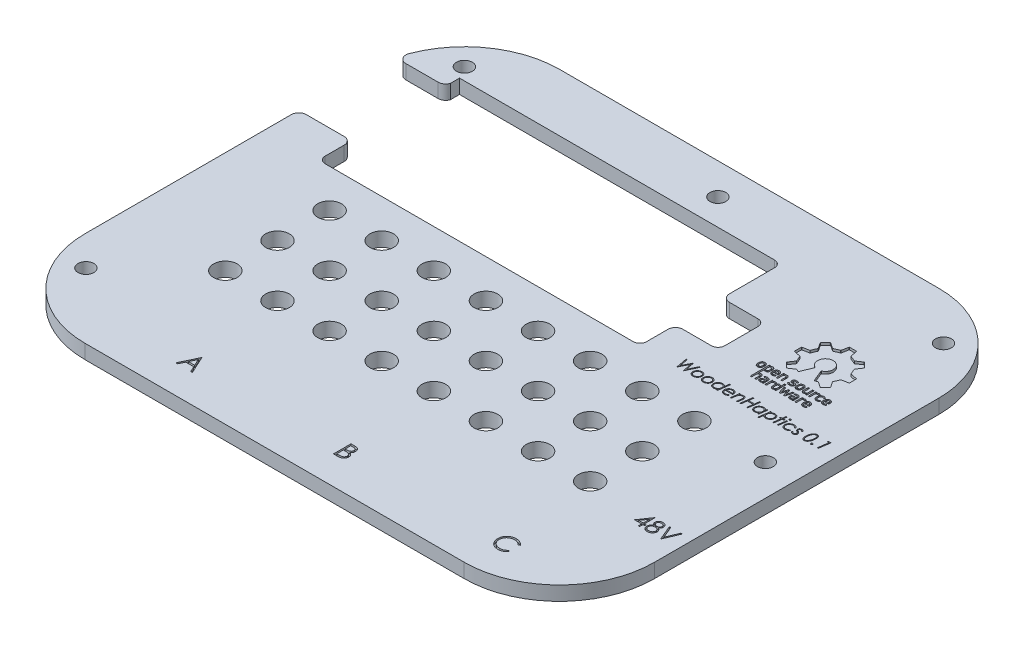
SolidWorks part; units mm, degrees
ref_plane "Front Plane" through (0, 0, 0) normal (0, 0, 1) x (1, 0, 0)
ref_plane "Top Plane" through (0, 0, 0) normal (0, 1, 0) x (1, 0, 0)
ref_plane "Right Plane" through (0, 0, 0) normal (1, 0, 0) x (0, 0, -1)
sketch "Sketch1" plane through (0, 0, 0) normal (0, 1, 0) x (1, 0, 0)
  line L0 (-60, 30) -> (-60, -30)
  line L1 (-40, 50) -> (40, 50)
  line L2 (-40, -50) -> (40, -50)
  line L3 (0, 50) -> (0, -50) construction
  line L4 (-60, 0) -> (94.7381, 0) construction
  line L5 (60, 0) -> (-94.7381, 0) construction
  line L6 (60, 30) -> (60, -30)
  arc A0 (-40, 50) -> (-60, 30) centre (-40, 30) ccw
  arc A1 (-40, -50) -> (-60, -30) centre (-40, -30) cw
  arc A2 (40, -50) -> (60, -30) centre (40, -30) ccw
  arc A3 (40, 50) -> (60, 30) centre (40, 30) cw
  dimension "D1" = 20
  dimension "D2" = 120
  dimension "D3" = 100
extrude "Boss-Extrude1" add sketch "Sketch1" along normal blind 3
sketch "Sketch2" plane through (0, 3, 0) normal (0, 1, 0) x (1, 0, 0)
  line L0 (-60, 30) -> (-60, -30) construction
  line L1 (-49, 38) -> (19, 38)
  line L2 (-60, 38) -> (-60, 9) construction
  line L3 (-49, 8) -> (19, 8)
  line L4 (28, 37) -> (28, 14) construction
  line L5 (-60, 35) -> (-49, 35)
  line L6 (-49, 35) -> (-49, 38)
  line L7 (40, 50) -> (-40, 50) construction
  line L8 (19, 38) -> (19, 25.5)
  line L9 (19, 25.5) -> (28, 25.5)
  line L10 (19, 8) -> (19, 15.5)
  line L11 (19, 15.5) -> (28, 15.5)
  line L12 (-60, 35) -> (-60, 15)
  line L13 (28, 25.5) -> (28, 15.5)
  line L14 (-49, 8) -> (-49, 15)
  line L15 (-49, 15) -> (-60, 15)
  dimension "D1" = 3
  dimension "D2" = 88
  dimension "D3" = 12
  dimension "D4" = 30
  dimension "D5" = 11
  dimension "D6" = 9
  dimension "D7" = 7.5
  dimension "D8" = 10
  dimension "D9" = 20
extrude "Cut-Extrude1" cut sketch "Sketch2" against normal through all
fillet "Fillet1" radius 1.5 11 edges at (19, 1.5, -8) (19, 1.5, -15.5) (28, 1.5, -15.5) (28, 1.5, -25.5) (19, 1.5, -38) (-49, 1.5, -35) (-60, 1.5, -15) (-49, 1.5, -15) (-49, 1.5, -8) (-59.3649, 1.5, -35) (19, 1.5, -25.5)
sketch "Sketch7" plane through (0, 3, 0) normal (0, 1, 0) x (1, 0, 0)
  line L0 (50.5586, 40.5086) -> (0, 0) construction
  line L1 (-50.5586, 40.5086) -> (0, 0) construction
  line L2 (0, 0) -> (-53.7093, -36.2274) construction
  line L3 (0, 0) -> (-58.4894, 0) construction
  circle A0 centre (53.475, 0) radius 1.75
  circle A1 centre (-53.7093, -36.2274) radius 1.75
  circle A2 centre (0, 43.45) radius 1.75
  circle A3 centre (50.5586, 40.5086) radius 1.75
  circle A4 centre (-50.5586, 40.5086) radius 1.75
  dimension "D1" = 3.5
  dimension "D2" = 43.45
  dimension "D3" = 64.7851
  dimension "D4" = 141.298
  dimension "D5" = 38.702
  dimension "D6" = 34
  dimension "D7" = 64.7851
  dimension "D8" = 64.7851
  dimension "D9" = 53.475
extrude "Cut-Extrude4" cut sketch "Sketch7" against normal through all
other "Move Face1" face at (-50.5586, 0, -42.2586) face at (-53.9103, 1.5, -35) face at (-49.5947, 1.5, -35.5947) face at (-15.75, 1.5, -38) face at (18.4053, 1.5, -37.4053) face at (19, 1.5, -31.75) face at (19.5947, 1.5, -26.0947) face at (23.5, 1.5, -25.5) face at (27.4053, 1.5, -24.9053) face at (28, 1.5, -20.5) face at (27.4053, 1.5, -16.0947) face at (23.5, 1.5, -15.5) face at (19.5947, 1.5, -14.9053) face at (19, 1.5, -11.75) face at (18.4053, 1.5, -8.5947) face at (-15, 1.5, -8) face at (-48.4053, 1.5, -8.5947) face at (-49, 1.5, -11.5) face at (-49.5947, 1.5, -14.4053) face at (-58.2881, 1.5, -35.8296) face at (-54.5, 1.5, -15) face at (-59.4053, 1.5, -14.4053) face at (-50.3762, 1.5, -44.9767) face at (0, 1.5, -50) face at (52.0711, 1.5, -42.0711) face at (60, 1.5, 0) face at (52.0711, 1.5, 42.0711) face at (-52.0711, 1.5, 42.0711) face at (-60, 1.5, 8.25) face at (0, 1.5, 50) face at (53.475, 0, 1.75) face at (0, 0, -41.7) face at (50.5586, 0, -38.7586) face at (-53.7093, 0, 37.9774) offset 0.08 parameters "D1"=0.08
sketch "Sketch8" plane through (0, 3, 0) normal (0, 1, 0) x (1, 0, 0)
  line L1 (-38.5, 0) -> (-60.08, 0) construction
  line L2 (-60.08, 13.5) -> (-60.08, -30) construction
  line L3 (38.5, 0) -> (60.08, 0) construction
  line L4 (60.08, -30) -> (60.08, 30) construction
  circle A0 centre (-38.5, 0) radius 2.5
  circle A1 centre (-27.5, 0) radius 2.5
  circle A2 centre (-16.5, 0) radius 2.5
  circle A3 centre (-5.5, 0) radius 2.5
  circle A4 centre (5.5, 0) radius 2.5
  circle A5 centre (16.5, 0) radius 2.5
  circle A6 centre (27.5, 0) radius 2.5
  circle A7 centre (38.5, 0) radius 2.5
  circle A10 centre (-27.5, -11) radius 2.5
  circle A11 centre (-16.5, -11) radius 2.5
  circle A12 centre (-5.5, -11) radius 2.5
  circle A13 centre (5.5, -11) radius 2.5
  circle A14 centre (16.5, -11) radius 2.5
  circle A15 centre (27.5, -11) radius 2.5
  circle A16 centre (38.5, -11) radius 2.5
  circle A19 centre (-27.5, -22) radius 2.5
  circle A20 centre (-16.5, -22) radius 2.5
  circle A21 centre (-5.5, -22) radius 2.5
  circle A22 centre (5.5, -22) radius 2.5
  circle A23 centre (16.5, -22) radius 2.5
  circle A24 centre (27.5, -22) radius 2.5
  circle A25 centre (38.5, -22) radius 2.5
  circle A37 centre (-38.5, -11) radius 2.5
  circle A38 centre (-38.5, -22) radius 2.5
  dimension "D3" = 5
  dimension "D4" = 11
  dimension "D5" = 11
  dimension "D1" = 8
  dimension "D2" = 3
extrude "Cut-Extrude5" cut sketch "Sketch8" against normal through all
sketch "Sketch9" plane through (0, 3, 0) normal (0, 1, 0) x (1, 0, 0)
  line L0 (-40, -50.08) -> (40, -50.08) construction
  line L1 (-60.08, 13.5) -> (-60.08, -30) construction
  line L2 (60.08, -30) -> (60.08, 30) construction
  text T0 "A" font "Century Gothic" height in points 14
  text T1 "B" font "Century Gothic" height in points 14
  text T2 "C" font "Century Gothic" height in points 14
  text T3 "48V" font "Century Gothic" height in points 12
  dimension "D1" = 6
  dimension "D2" = 33
  dimension "D3" = 33
  dimension "D4" = 33
  dimension "D5" = 10
  dimension "D6" = 25
extrude "Cut-Extrude6" cut sketch "Sketch9" against normal blind 0.5
sketch "Sketch10" plane through (0, 3, 0) normal (0, 1, 0) x (1, 0, 0)
  line L0 (60.08, -30) -> (60.08, 30) construction
  line L1 (40, 50.08) -> (-40, 50.08) construction
  line L2 (-47.5, 8.08) -> (17.5, 8.08) construction
  text T0 "WoodenHaptics 0.1" font "Century Gothic" height in points 9
  line B0 (45.5559, 14.1483) -> (45.5559, 15.6998)
  line B1 (45.5559, 15.6998) -> (45.8679, 15.6998)
  line B2 (45.8679, 15.6998) -> (45.8679, 15.5341)
  line B3 (45.8679, 15.5341) -> (45.8737, 15.5341)
  line B4 (46.6017, 15.5979) -> (46.3765, 15.3289)
  line B5 (45.8679, 15.0808) -> (45.8679, 14.1483)
  line B6 (45.8679, 14.1483) -> (45.5559, 14.1483)
  line B7 (43.1466, 14.1483) -> (42.8217, 15.2335)
  line B8 (42.8217, 15.2335) -> (42.8159, 15.2335)
  line B9 (42.8159, 15.2335) -> (42.4917, 14.1483)
  line B10 (42.4917, 14.1483) -> (42.2163, 14.1483)
  line B11 (42.2163, 14.1483) -> (41.7206, 15.6998)
  line B12 (41.7206, 15.6998) -> (42.0506, 15.6998)
  line B13 (42.0506, 15.6998) -> (42.3483, 14.6131)
  line B14 (42.3483, 14.6131) -> (42.354, 14.6131)
  line B15 (42.354, 14.6131) -> (42.7054, 15.6998)
  line B16 (42.7054, 15.6998) -> (42.9328, 15.6998)
  line B17 (42.9328, 15.6998) -> (43.2836, 14.6131)
  line B18 (43.2836, 14.6131) -> (43.29, 14.6131)
  line B19 (43.29, 14.6131) -> (43.587, 15.6998)
  line B20 (43.587, 15.6998) -> (43.9176, 15.6998)
  line B21 (43.9176, 15.6998) -> (43.4213, 14.1483)
  line B22 (43.4213, 14.1483) -> (43.1466, 14.1483)
  line B23 (38.9018, 17.2752) -> (37.9356, 17.2752)
  line B24 (38.6457, 17.0421) -> (38.8717, 16.8492)
  line B25 (38.9018, 17.532) -> (38.9018, 17.2752)
  line B26 (38.5642, 14.1426) -> (38.5642, 14.2796)
  line B27 (38.5642, 14.2796) -> (38.5577, 14.2796)
  line B28 (38.1439, 15.0585) -> (38.5642, 15.0585)
  line B29 (38.5642, 15.0585) -> (38.5642, 15.2228)
  line B30 (37.9688, 15.3024) -> (37.73, 15.4903)
  line B31 (38.8661, 15.2048) -> (38.8661, 14.1426)
  line B32 (38.8661, 14.1426) -> (38.5642, 14.1426)
  line B33 (37.9356, 17.532) -> (38.5905, 17.532)
  line B34 (38.5642, 14.6877) -> (38.5642, 14.8017)
  line B35 (38.5642, 14.8017) -> (38.2005, 14.8017)
  line B36 (47.998, 17.0737) -> (48.2282, 16.8671)
  line B37 (48.2282, 17.9179) -> (47.998, 17.7127)
  line B38 (35.5537, 17.3914) -> (35.5494, 17.5356)
  line B39 (34.9027, 17.5365) -> (34.8988, 17.395)
  line B40 (34.8988, 17.395) -> (34.9027, 17.2496)
  line B41 (35.5494, 17.2478) -> (35.5537, 17.3914)
  line B42 (43.7636, 17.3914) -> (43.7593, 17.5356)
  line B43 (43.1127, 17.5365) -> (43.1087, 17.395)
  line B44 (43.1087, 17.395) -> (43.1127, 17.2496)
  line B45 (43.7593, 17.2478) -> (43.7636, 17.3914)
  line B46 (39.1746, 16.6175) -> (39.1746, 18.1689)
  line B47 (39.1746, 18.1689) -> (39.4867, 18.1689)
  line B48 (39.4867, 18.1689) -> (39.4867, 18.0032)
  line B49 (39.4867, 18.0032) -> (39.4924, 18.0032)
  line B50 (40.4133, 17.6489) -> (40.4133, 16.6175)
  line B51 (40.4133, 16.6175) -> (40.1013, 16.6175)
  line B52 (40.1013, 16.6175) -> (40.1013, 17.5413)
  line B53 (39.4867, 17.5413) -> (39.4867, 16.6175)
  line B54 (39.4867, 16.6175) -> (39.1746, 16.6175)
  line B55 (44.887, 14.1426) -> (44.887, 14.2796)
  line B56 (44.887, 14.2796) -> (44.8805, 14.2796)
  line B57 (44.4667, 15.0585) -> (44.887, 15.0585)
  line B58 (44.887, 15.0585) -> (44.887, 15.2228)
  line B59 (44.2916, 15.3024) -> (44.0528, 15.4903)
  line B60 (45.1889, 15.2048) -> (45.1889, 14.1426)
  line B61 (45.1889, 14.1426) -> (44.887, 14.1426)
  line B62 (47.8997, 14.806) -> (46.9336, 14.806)
  line B63 (47.6437, 14.5729) -> (47.8696, 14.38)
  line B64 (47.8997, 15.0628) -> (47.8997, 14.806)
  line B65 (39.2283, 14.1483) -> (39.2283, 15.6998)
  line B66 (39.2283, 15.6998) -> (39.5403, 15.6998)
  line B67 (39.5403, 15.6998) -> (39.5403, 15.5341)
  line B68 (39.5403, 15.5341) -> (39.5461, 15.5341)
  line B69 (40.2741, 15.5979) -> (40.0489, 15.3289)
  line B70 (39.5403, 15.0808) -> (39.5403, 14.1483)
  line B71 (39.5403, 14.1483) -> (39.2283, 14.1483)
  line B72 (46.9336, 15.0628) -> (47.5885, 15.0628)
  line B73 (44.887, 14.6877) -> (44.887, 14.8017)
  line B74 (44.887, 14.8017) -> (44.5233, 14.8017)
  line B75 (44.3583, 17.1375) -> (44.3583, 18.1689)
  line B76 (44.3583, 18.1689) -> (44.6703, 18.1689)
  line B77 (44.6703, 18.1689) -> (44.6703, 17.2437)
  line B78 (45.285, 17.2437) -> (45.285, 18.1689)
  line B79 (45.285, 18.1689) -> (45.597, 18.1689)
  line B80 (45.597, 18.1689) -> (45.597, 16.6175)
  line B81 (45.597, 16.6175) -> (45.285, 16.6175)
  line B82 (45.285, 16.6175) -> (45.285, 16.7817)
  line B83 (45.285, 16.7817) -> (45.2786, 16.7817)
  line B84 (45.9512, 16.6175) -> (45.9512, 18.1689)
  line B85 (45.9512, 18.1689) -> (46.2633, 18.1689)
  line B86 (46.2633, 18.1689) -> (46.2633, 18.0032)
  line B87 (46.2633, 18.0032) -> (46.269, 18.0032)
  line B88 (46.997, 18.0671) -> (46.7718, 17.7981)
  line B89 (46.2633, 17.5499) -> (46.2633, 16.6175)
  line B90 (46.2633, 16.6175) -> (45.9512, 16.6175)
  line B91 (41.2207, 14.1483) -> (41.2207, 14.3097)
  line B92 (40.2996, 14.682) -> (40.2941, 14.9258)
  line B93 (40.2941, 14.9258) -> (40.2996, 15.1666)
  line B94 (41.2207, 15.5341) -> (41.2207, 16.3259)
  line B95 (41.2207, 16.3259) -> (41.5328, 16.3259)
  line B96 (41.5328, 16.3259) -> (41.5328, 14.1483)
  line B97 (41.5328, 14.1483) -> (41.2207, 14.1483)
  line B98 (49.598, 17.2752) -> (48.6319, 17.2752)
  line B99 (49.3419, 17.0421) -> (49.5679, 16.8492)
  line B100 (49.598, 17.532) -> (49.598, 17.2752)
  line B101 (41.2772, 16.8757) -> (41.4953, 17.0916)
  line B102 (42.1006, 17.2437) -> (41.8259, 17.2695)
  line B103 (42.5654, 17.976) -> (42.3725, 17.7486)
  line B104 (41.8962, 17.5593) -> (42.153, 17.5413)
  line B105 (48.6319, 17.532) -> (49.2867, 17.532)
  line B106 (36.1508, 14.1483) -> (36.1508, 18.1689)
  line B107 (36.1508, 18.1689) -> (36.4628, 18.1689)
  line B108 (36.4628, 18.1689) -> (36.4628, 18.0061)
  line B109 (37.3838, 17.6349) -> (37.3895, 17.3914)
  line B110 (37.3895, 17.3914) -> (37.3838, 17.1493)
  line B111 (36.4628, 16.7817) -> (36.4628, 15.5341)
  line B112 (36.4628, 15.5341) -> (36.4685, 15.5341)
  line B113 (37.3895, 15.1797) -> (37.3895, 14.1483)
  line B114 (37.3895, 14.1483) -> (37.0775, 14.1483)
  line B115 (37.0775, 14.1483) -> (37.0775, 15.0722)
  line B116 (36.4628, 15.0722) -> (36.4628, 14.1483)
  line B117 (36.4628, 14.1483) -> (36.1508, 14.1483)
  line B118 (41.4319, 22.4926) -> (40.4479, 20.0828)
  line B119 (40.3498, 20.0418) -> (39.8153, 20.2632)
  line B120 (39.7446, 20.256) -> (38.5692, 19.4608)
  line B121 (38.4742, 19.4699) -> (37.4699, 20.4742)
  line B122 (37.4608, 20.5692) -> (38.256, 21.7446)
  line B123 (38.2632, 21.8153) -> (37.7798, 22.9825)
  line B124 (37.7247, 23.0274) -> (36.3313, 23.2963)
  line B125 (36.2705, 23.3699) -> (36.2705, 24.7901)
  line B126 (36.3313, 24.8637) -> (37.7247, 25.1326)
  line B127 (37.7798, 25.1775) -> (38.2632, 26.3447)
  line B128 (38.256, 26.4154) -> (37.4608, 27.5908)
  line B129 (37.4699, 27.6858) -> (38.4742, 28.6901)
  line B130 (38.5692, 28.6992) -> (39.7446, 27.904)
  line B131 (39.8153, 27.8968) -> (40.9825, 28.3802)
  line B132 (41.0274, 28.4353) -> (41.2963, 29.8287)
  line B133 (41.3699, 29.8895) -> (42.7901, 29.8895)
  line B134 (42.8637, 29.8287) -> (43.1326, 28.4353)
  line B135 (43.1775, 28.3802) -> (44.3447, 27.8968)
  line B136 (44.4154, 27.904) -> (45.5908, 28.6992)
  line B137 (45.6858, 28.6901) -> (46.6901, 27.6858)
  line B138 (46.6992, 27.5908) -> (45.904, 26.4154)
  line B139 (45.8968, 26.3447) -> (46.3802, 25.1775)
  line B140 (46.4353, 25.1326) -> (47.8287, 24.8637)
  line B141 (47.8895, 24.7901) -> (47.8895, 23.3699)
  line B142 (47.8287, 23.2963) -> (46.4353, 23.0274)
  line B143 (46.3802, 22.9825) -> (45.8968, 21.8153)
  line B144 (45.904, 21.7446) -> (46.6992, 20.5692)
  line B145 (46.6901, 20.4742) -> (45.6858, 19.4699)
  line B146 (45.5908, 19.4608) -> (44.4154, 20.256)
  line B147 (44.3447, 20.2632) -> (43.8102, 20.0418)
  line B148 (43.7121, 20.0828) -> (42.7281, 22.4926)
  arc B149 (46.0474, 15.6718) -> (45.8737, 15.5341) centre (46.2419, 15.248) ccw
  arc B150 (46.2775, 15.7177) -> (46.0474, 15.6718) centre (46.2676, 15.1676) ccw
  arc B151 (46.4439, 15.6877) -> (46.2775, 15.7177) centre (46.2776, 15.2413) ccw
  arc B152 (46.6017, 15.5979) -> (46.4439, 15.6877) centre (46.2351, 15.1374) ccw
  arc B153 (46.3765, 15.3289) -> (46.2739, 15.3865) centre (46.1283, 15.0069) ccw
  arc B154 (46.2739, 15.3865) -> (46.1699, 15.4057) centre (46.1689, 15.1091) ccw
  arc B155 (46.1699, 15.4057) -> (45.9615, 15.3286) centre (46.1698, 15.086) ccw
  arc B156 (45.9615, 15.3286) -> (45.8913, 15.2281) centre (46.1121, 15.1486) ccw
  arc B157 (45.8913, 15.2281) -> (45.8679, 15.0808) centre (46.2848, 15.0901) ccw
  arc B158 (40.9152, 15.4057) -> (40.8158, 15.3962) centre (40.9104, 14.9279) ccw
  arc B159 (40.8158, 15.3962) -> (40.7385, 15.3679) centre (40.8684, 15.1327) ccw
  arc B160 (40.7385, 15.3679) -> (40.6502, 15.2547) centre (40.8286, 15.2066) ccw
  arc B161 (40.6502, 15.2547) -> (40.6061, 14.9258) centre (41.7747, 14.9365) ccw
  arc B162 (40.6061, 14.9258) -> (40.6502, 14.5919) centre (41.7939, 14.9129) ccw
  arc B163 (40.6502, 14.5919) -> (40.7385, 14.4787) centre (40.8286, 14.64) ccw
  arc B164 (40.7385, 14.4787) -> (40.8158, 14.4504) centre (40.8684, 14.7139) ccw
  arc B165 (40.8158, 14.4504) -> (40.9152, 14.441) centre (40.9104, 14.9187) ccw
  arc B166 (40.9152, 14.441) -> (41.013, 14.4508) centre (40.9199, 14.8867) ccw
  arc B167 (41.013, 14.4508) -> (41.0892, 14.4802) centre (40.9598, 14.7019) ccw
  arc B168 (41.0892, 14.4802) -> (41.1766, 14.598) centre (40.9903, 14.645) ccw
  arc B169 (41.1766, 14.598) -> (41.2207, 14.9258) centre (40.014, 14.9214) ccw
  arc B170 (41.2207, 14.9258) -> (41.1766, 15.2486) centre (40.0326, 14.9278) ccw
  arc B171 (41.1766, 15.2486) -> (41.0892, 15.3664) centre (40.9903, 15.2017) ccw
  arc B172 (41.0892, 15.3664) -> (41.013, 15.3959) centre (40.9598, 15.1448) ccw
  arc B173 (41.013, 15.3959) -> (40.9152, 15.4057) centre (40.9199, 14.9599) ccw
  arc B174 (37.9356, 17.2752) -> (37.9616, 17.1076) centre (38.4273, 17.2657) ccw
  arc B175 (37.9616, 17.1076) -> (38.0397, 16.988) centre (38.2422, 17.2052) ccw
  arc B176 (38.0397, 16.988) -> (38.158, 16.9161) centre (38.2751, 17.2426) ccw
  arc B177 (38.158, 16.9161) -> (38.305, 16.8922) centre (38.2997, 17.3228) ccw
  arc B178 (38.305, 16.8922) -> (38.4867, 16.9297) centre (38.3077, 17.3382) ccw
  arc B179 (38.4867, 16.9297) -> (38.6457, 17.0421) centre (38.2742, 17.3989) ccw
  arc B180 (38.749, 16.7337) -> (38.8717, 16.8492) centre (38.3008, 17.3326) ccw
  arc B181 (38.612, 16.6569) -> (38.749, 16.7337) centre (38.3864, 17.2203) ccw
  arc B182 (38.3108, 16.5996) -> (38.612, 16.6569) centre (38.3131, 17.4068) ccw
  arc B183 (38.0756, 16.6382) -> (38.3108, 16.5996) centre (38.3113, 17.3377) ccw
  arc B184 (37.8478, 16.7541) -> (38.0756, 16.6382) centre (38.3697, 17.4979) ccw
  arc B185 (37.7497, 16.8517) -> (37.8478, 16.7541) centre (38.0749, 17.0805) ccw
  arc B186 (37.6797, 16.9897) -> (37.7497, 16.8517) centre (38.2048, 17.1694) ccw
  arc B187 (37.6376, 17.1681) -> (37.6797, 16.9897) centre (38.5501, 17.2888) ccw
  arc B188 (37.6236, 17.3871) -> (37.6376, 17.1681) centre (39.1986, 17.378) ccw
  arc B189 (37.6366, 17.5963) -> (37.6236, 17.3871) centre (39.1924, 17.3951) ccw
  arc B190 (37.6754, 17.7704) -> (37.6366, 17.5963) centre (38.5979, 17.4735) ccw
  arc B191 (37.74, 17.9095) -> (37.6754, 17.7704) centre (38.2635, 17.5816) ccw
  arc B192 (37.8306, 18.0136) -> (37.74, 17.9095) centre (38.1213, 17.6695) ccw
  arc B193 (38.0423, 18.1436) -> (37.8306, 18.0136) centre (38.3428, 17.4164) ccw
  arc B194 (38.2634, 18.1869) -> (38.0423, 18.1436) centre (38.2642, 17.5964) ccw
  arc B195 (38.5028, 18.1426) -> (38.2634, 18.1869) centre (38.2682, 17.5433) ccw
  arc B196 (38.7103, 18.0097) -> (38.5028, 18.1426) centre (38.2533, 17.5245) ccw
  arc B197 (38.8539, 17.8017) -> (38.7103, 18.0097) centre (38.3261, 17.5908) ccw
  arc B198 (38.9018, 17.532) -> (38.8539, 17.8017) centre (38.1824, 17.5434) ccw
  arc B199 (34.5958, 17.6128) -> (34.5861, 17.395) centre (36.7, 17.4092) ccw
  arc B200 (34.6252, 17.7669) -> (34.5958, 17.6128) centre (35.3793, 17.5436) ccw
  arc B201 (34.7539, 17.9882) -> (34.6252, 17.7669) centre (35.1945, 17.5837) ccw
  arc B202 (34.83, 18.0569) -> (34.7539, 17.9882) centre (35.1672, 17.6072) ccw
  arc B203 (34.9307, 18.1227) -> (34.83, 18.0569) centre (35.3735, 17.3342) ccw
  arc B204 (35.061, 18.1708) -> (34.9307, 18.1227) centre (35.1535, 17.7201) ccw
  arc B205 (35.2259, 18.1869) -> (35.061, 18.1708) centre (35.2184, 17.409) ccw
  arc B206 (35.3888, 18.1708) -> (35.2259, 18.1869) centre (35.233, 17.4241) ccw
  arc B207 (35.5189, 18.1227) -> (35.3888, 18.1708) centre (35.294, 17.7148) ccw
  arc B208 (35.6203, 18.0569) -> (35.5189, 18.1227) centre (35.072, 17.3221) ccw
  arc B209 (35.6971, 17.9882) -> (35.6203, 18.0569) centre (35.2799, 17.5994) ccw
  arc B210 (35.8255, 17.7669) -> (35.6971, 17.9882) centre (35.2597, 17.5865) ccw
  arc B211 (35.8546, 17.6128) -> (35.8255, 17.7669) centre (35.0646, 17.5437) ccw
  arc B212 (35.8642, 17.395) -> (35.8546, 17.6128) centre (33.7309, 17.4093) ccw
  arc B213 (35.8546, 17.1735) -> (35.8642, 17.395) centre (33.6634, 17.3802) ccw
  arc B214 (35.8255, 17.0181) -> (35.8546, 17.1735) centre (35.0621, 17.2412) ccw
  arc B215 (35.6971, 16.7968) -> (35.8255, 17.0181) centre (35.2597, 17.1985) ccw
  arc B216 (35.6203, 16.7273) -> (35.6971, 16.7968) centre (35.2965, 17.1626) ccw
  arc B217 (35.5189, 16.6623) -> (35.6203, 16.7273) centre (35.1111, 17.41) ccw
  arc B218 (35.3888, 16.6152) -> (35.5189, 16.6623) centre (35.2948, 17.0783) ccw
  arc B219 (35.2259, 16.5996) -> (35.3888, 16.6152) centre (35.233, 17.3791) ccw
  arc B220 (35.061, 16.6152) -> (35.2259, 16.5996) centre (35.2183, 17.3946) ccw
  arc B221 (34.9307, 16.6623) -> (35.061, 16.6152) centre (35.1527, 17.0729) ccw
  arc B222 (34.83, 16.7273) -> (34.9307, 16.6623) centre (35.335, 17.399) ccw
  arc B223 (34.7539, 16.7968) -> (34.83, 16.7273) centre (35.151, 17.1554) ccw
  arc B224 (34.6252, 17.0181) -> (34.7539, 16.7968) centre (35.1945, 17.2012) ccw
  arc B225 (34.5958, 17.1735) -> (34.6252, 17.0181) centre (35.3818, 17.2413) ccw
  arc B226 (34.5861, 17.395) -> (34.5958, 17.1735) centre (36.7668, 17.3802) ccw
  arc B227 (42.8058, 17.6128) -> (42.796, 17.395) centre (44.9099, 17.4092) ccw
  arc B228 (42.8351, 17.7669) -> (42.8058, 17.6128) centre (43.5892, 17.5437) ccw
  arc B229 (42.9638, 17.9882) -> (42.8351, 17.7669) centre (43.4044, 17.5837) ccw
  arc B230 (43.0399, 18.0569) -> (42.9638, 17.9882) centre (43.3772, 17.6072) ccw
  arc B231 (43.1407, 18.1227) -> (43.0399, 18.0569) centre (43.5835, 17.334) ccw
  arc B232 (43.2709, 18.1708) -> (43.1407, 18.1227) centre (43.3635, 17.7201) ccw
  arc B233 (43.4358, 18.1869) -> (43.2709, 18.1708) centre (43.4283, 17.4091) ccw
  arc B234 (43.5987, 18.1708) -> (43.4358, 18.1869) centre (43.4429, 17.4241) ccw
  arc B235 (43.7288, 18.1227) -> (43.5987, 18.1708) centre (43.5039, 17.7148) ccw
  arc B236 (43.8302, 18.0569) -> (43.7288, 18.1227) centre (43.282, 17.3221) ccw
  arc B237 (43.907, 17.9882) -> (43.8302, 18.0569) centre (43.4899, 17.5993) ccw
  arc B238 (44.0354, 17.7669) -> (43.907, 17.9882) centre (43.4696, 17.5865) ccw
  arc B239 (44.0645, 17.6128) -> (44.0354, 17.7669) centre (43.2745, 17.5436) ccw
  arc B240 (44.0742, 17.395) -> (44.0645, 17.6128) centre (41.9408, 17.4092) ccw
  arc B241 (44.0645, 17.1735) -> (44.0742, 17.395) centre (41.8734, 17.3802) ccw
  arc B242 (44.0354, 17.0181) -> (44.0645, 17.1735) centre (43.272, 17.2413) ccw
  arc B243 (43.907, 16.7968) -> (44.0354, 17.0181) centre (43.4696, 17.1985) ccw
  arc B244 (43.8302, 16.7273) -> (43.907, 16.7968) centre (43.5064, 17.1626) ccw
  arc B245 (43.7288, 16.6623) -> (43.8302, 16.7273) centre (43.321, 17.41) ccw
  arc B246 (43.5987, 16.6152) -> (43.7288, 16.6623) centre (43.5047, 17.0783) ccw
  arc B247 (43.4358, 16.5996) -> (43.5987, 16.6152) centre (43.4429, 17.3792) ccw
  arc B248 (43.2709, 16.6152) -> (43.4358, 16.5996) centre (43.4283, 17.3944) ccw
  arc B249 (43.1407, 16.6623) -> (43.2709, 16.6152) centre (43.3627, 17.0729) ccw
  arc B250 (43.0399, 16.7273) -> (43.1407, 16.6623) centre (43.5449, 17.3992) ccw
  arc B251 (42.9638, 16.7968) -> (43.0399, 16.7273) centre (43.3609, 17.1553) ccw
  arc B252 (42.8351, 17.0181) -> (42.9638, 16.7968) centre (43.4044, 17.2013) ccw
  arc B253 (42.8058, 17.1735) -> (42.8351, 17.0181) centre (43.5917, 17.2411) ccw
  arc B254 (42.796, 17.395) -> (42.8058, 17.1735) centre (44.9768, 17.3803) ccw
  arc B255 (38.4279, 14.1634) -> (38.5577, 14.2796) centre (38.3356, 14.3971) ccw
  arc B256 (38.321, 14.1343) -> (38.4279, 14.1634) centre (38.2525, 14.5976) ccw
  arc B257 (38.1855, 14.1246) -> (38.321, 14.1343) centre (38.1919, 14.9885) ccw
  arc B258 (37.9601, 14.1618) -> (38.1855, 14.1246) centre (38.1892, 14.8503) ccw
  arc B259 (37.7974, 14.2616) -> (37.9601, 14.1618) centre (38.0966, 14.5664) ccw
  arc B260 (37.6898, 14.4117) -> (37.7974, 14.2616) centre (38.0886, 14.584) ccw
  arc B261 (37.654, 14.598) -> (37.6898, 14.4117) centre (38.1242, 14.5919) ccw
  arc B262 (37.685, 14.7768) -> (37.654, 14.598) centre (38.1531, 14.6035) ccw
  arc B263 (37.7781, 14.9244) -> (37.685, 14.7768) centre (38.1003, 14.6181) ccw
  arc B264 (37.9312, 15.0236) -> (37.7781, 14.9244) centre (38.0614, 14.6547) ccw
  arc B265 (38.1439, 15.0585) -> (37.9312, 15.0236) centre (38.1397, 14.4196) ccw
  arc B266 (38.5642, 15.2228) -> (38.5454, 15.3128) centre (38.3684, 15.2288) ccw
  arc B267 (38.5454, 15.3128) -> (38.4874, 15.3763) centre (38.4019, 15.2401) ccw
  arc B268 (38.4874, 15.3763) -> (38.3904, 15.4132) centre (38.3412, 15.138) ccw
  arc B269 (38.3904, 15.4132) -> (38.2543, 15.4236) centre (38.2745, 14.7921) ccw
  arc B270 (38.2543, 15.4236) -> (38.1557, 15.4175) centre (38.2503, 14.6889) ccw
  arc B271 (38.1557, 15.4175) -> (38.075, 15.3992) centre (38.2104, 14.9891) ccw
  arc B272 (38.075, 15.3992) -> (37.9688, 15.3024) centre (38.1625, 15.1967) ccw
  arc B273 (37.9441, 15.6626) -> (37.73, 15.4903) centre (38.1619, 15.1729) ccw
  arc B274 (38.0815, 15.7043) -> (37.9441, 15.6626) centre (38.1866, 15.1099) ccw
  arc B275 (38.2393, 15.7163) -> (38.0815, 15.7043) centre (38.221, 14.9114) ccw
  arc B276 (38.4943, 15.6901) -> (38.2393, 15.7163) centre (38.2616, 14.6791) ccw
  arc B277 (38.694, 15.6058) -> (38.4943, 15.6901) centre (38.3526, 15.0755) ccw
  arc B278 (38.8213, 15.4464) -> (38.694, 15.6058) centre (38.4823, 15.3061) ccw
  arc B279 (38.854, 15.3359) -> (38.8213, 15.4464) centre (38.3423, 15.2446) ccw
  arc B280 (38.8661, 15.2048) -> (38.854, 15.3359) centre (38.0934, 15.1995) ccw
  arc B281 (38.5905, 17.532) -> (38.5623, 17.6865) centre (38.084, 17.5192) ccw
  arc B282 (38.5623, 17.6865) -> (38.4919, 17.7999) centre (38.2668, 17.5817) ccw
  arc B283 (38.4919, 17.7999) -> (38.3891, 17.8696) centre (38.2734, 17.5881) ccw
  arc B284 (38.3891, 17.8696) -> (38.2634, 17.8928) centre (38.2673, 17.5623) ccw
  arc B285 (38.2634, 17.8928) -> (38.1361, 17.8696) centre (38.2594, 17.5546) ccw
  arc B286 (38.1361, 17.8696) -> (38.0325, 17.7999) centre (38.2506, 17.5873) ccw
  arc B287 (38.0325, 17.7999) -> (37.9624, 17.6865) centre (38.2527, 17.5854) ccw
  arc B288 (37.9624, 17.6865) -> (37.9356, 17.532) centre (38.4313, 17.5258) ccw
  arc B289 (38.2005, 14.8017) -> (38.0843, 14.787) centre (38.2092, 14.2683) ccw
  arc B290 (38.0843, 14.787) -> (38.0018, 14.7506) centre (38.1401, 14.5487) ccw
  arc B291 (38.0018, 14.7506) -> (37.953, 14.6927) centre (38.0861, 14.6302) ccw
  arc B292 (37.953, 14.6927) -> (37.938, 14.6131) centre (38.1164, 14.6206) ccw
  arc B293 (37.938, 14.6131) -> (37.955, 14.5407) centre (38.0964, 14.6121) ccw
  arc B294 (37.955, 14.5407) -> (38.0062, 14.4783) centre (38.1325, 14.634) ccw
  arc B295 (38.0062, 14.4783) -> (38.0935, 14.4325) centre (38.1444, 14.636) ccw
  arc B296 (38.0935, 14.4325) -> (38.2235, 14.4173) centre (38.2145, 14.9029) ccw
  arc B297 (38.2235, 14.4173) -> (38.3861, 14.4275) centre (38.2491, 15.3079) ccw
  arc B298 (38.3861, 14.4275) -> (38.4924, 14.4639) centre (38.346, 14.7183) ccw
  arc B299 (38.4924, 14.4639) -> (38.5238, 14.4962) centre (38.4256, 14.5603) ccw
  arc B300 (38.5238, 14.4962) -> (38.5462, 14.5442) centre (38.3641, 14.5999) ccw
  arc B301 (38.5462, 14.5442) -> (38.5642, 14.6877) centre (38.085, 14.6748) ccw
  arc B302 (47.9865, 16.6749) -> (48.2282, 16.8671) centre (47.5838, 17.4294) ccw
  arc B303 (47.8375, 16.6184) -> (47.9865, 16.6749) centre (47.697, 17.2137) ccw
  arc B304 (47.6702, 16.5996) -> (47.8375, 16.6184) centre (47.6738, 17.3198) ccw
  arc B305 (47.4141, 16.6453) -> (47.6702, 16.5996) centre (47.6669, 17.321) ccw
  arc B306 (47.1839, 16.7825) -> (47.4141, 16.6453) centre (47.6964, 17.3808) ccw
  arc B307 (47.0888, 16.8891) -> (47.1839, 16.7825) centre (47.5106, 17.1696) ccw
  arc B308 (47.0209, 17.0261) -> (47.0888, 16.8891) centre (47.6063, 17.2308) ccw
  arc B309 (46.9801, 17.1936) -> (47.0209, 17.0261) centre (47.8567, 17.3183) ccw
  arc B310 (46.9665, 17.3914) -> (46.9801, 17.1936) centre (48.3139, 17.3846) ccw
  arc B311 (46.9801, 17.5894) -> (46.9665, 17.3914) centre (48.3162, 17.3982) ccw
  arc B312 (47.0209, 17.7571) -> (46.9801, 17.5894) centre (47.8617, 17.464) ccw
  arc B313 (47.0888, 17.8947) -> (47.0209, 17.7571) centre (47.6123, 17.5509) ccw
  arc B314 (47.1839, 18.0022) -> (47.0888, 17.8947) centre (47.5165, 17.6119) ccw
  arc B315 (47.4141, 18.1407) -> (47.1839, 18.0022) centre (47.6984, 17.4076) ccw
  arc B316 (47.6702, 18.1869) -> (47.4141, 18.1407) centre (47.6669, 17.4717) ccw
  arc B317 (47.8375, 18.1679) -> (47.6702, 18.1869) centre (47.6738, 17.4731) ccw
  arc B318 (47.9865, 18.1108) -> (47.8375, 18.1679) centre (47.6965, 17.5763) ccw
  arc B319 (48.2282, 17.9179) -> (47.9865, 18.1108) centre (47.5758, 17.3483) ccw
  arc B320 (47.998, 17.7127) -> (47.8531, 17.8343) centre (47.637, 17.4297) ccw
  arc B321 (47.8531, 17.8343) -> (47.6824, 17.8749) centre (47.6851, 17.5067) ccw
  arc B322 (47.6824, 17.8749) -> (47.5057, 17.8446) centre (47.6726, 17.4001) ccw
  arc B323 (47.5057, 17.8446) -> (47.3795, 17.754) centre (47.6191, 17.5536) ccw
  arc B324 (47.3795, 17.754) -> (47.3038, 17.6029) centre (47.6904, 17.5037) ccw
  arc B325 (47.3038, 17.6029) -> (47.2785, 17.3914) centre (48.0709, 17.4041) ccw
  arc B326 (47.2785, 17.3914) -> (47.3038, 17.1809) centre (48.0641, 17.3788) ccw
  arc B327 (47.3038, 17.1809) -> (47.3795, 17.0304) centre (47.6879, 17.2799) ccw
  arc B328 (47.3795, 17.0304) -> (47.5057, 16.9402) centre (47.6185, 17.2314) ccw
  arc B329 (47.5057, 16.9402) -> (47.6824, 16.9101) centre (47.6726, 17.3867) ccw
  arc B330 (47.6824, 16.9101) -> (47.8538, 16.951) centre (47.6854, 17.2772) ccw
  arc B331 (47.8538, 16.951) -> (47.998, 17.0737) centre (47.6393, 17.3492) ccw
  arc B332 (35.5494, 17.5356) -> (35.5364, 17.6295) centre (34.9733, 17.5043) ccw
  arc B333 (35.5364, 17.6295) -> (35.4769, 17.7608) centre (35.1391, 17.5285) ccw
  arc B334 (35.4769, 17.7608) -> (35.3733, 17.8463) centre (35.2679, 17.6131) ccw
  arc B335 (35.3733, 17.8463) -> (35.2259, 17.8749) centre (35.2339, 17.5213) ccw
  arc B336 (35.2259, 17.8749) -> (35.0774, 17.8463) centre (35.2173, 17.5185) ccw
  arc B337 (35.0774, 17.8463) -> (34.9748, 17.7608) centre (35.1793, 17.6199) ccw
  arc B338 (34.9748, 17.7608) -> (34.9146, 17.6295) centre (35.2708, 17.5455) ccw
  arc B339 (34.9146, 17.6295) -> (34.9027, 17.5365) centre (35.5245, 17.5047) ccw
  arc B340 (34.9027, 17.2496) -> (34.9146, 17.1547) centre (35.5407, 17.281) ccw
  arc B341 (34.9146, 17.1547) -> (34.9748, 17.0242) centre (35.2577, 17.2339) ccw
  arc B342 (34.9748, 17.0242) -> (35.0774, 16.9386) centre (35.1792, 17.165) ccw
  arc B343 (35.0774, 16.9386) -> (35.2259, 16.9101) centre (35.2173, 17.2665) ccw
  arc B344 (35.2259, 16.9101) -> (35.3733, 16.9386) centre (35.2339, 17.2636) ccw
  arc B345 (35.3733, 16.9386) -> (35.4769, 17.0242) centre (35.2679, 17.1718) ccw
  arc B346 (35.4769, 17.0242) -> (35.5364, 17.154) centre (35.1546, 17.2505) ccw
  arc B347 (35.5364, 17.154) -> (35.5494, 17.2478) centre (34.9739, 17.2792) ccw
  arc B348 (43.7593, 17.5356) -> (43.7464, 17.6295) centre (43.1832, 17.5044) ccw
  arc B349 (43.7464, 17.6295) -> (43.6868, 17.7608) centre (43.3491, 17.5285) ccw
  arc B350 (43.6868, 17.7608) -> (43.5832, 17.8463) centre (43.4779, 17.6131) ccw
  arc B351 (43.5832, 17.8463) -> (43.4358, 17.8749) centre (43.4439, 17.5213) ccw
  arc B352 (43.4358, 17.8749) -> (43.2873, 17.8463) centre (43.4273, 17.5185) ccw
  arc B353 (43.2873, 17.8463) -> (43.1848, 17.7608) centre (43.3892, 17.62) ccw
  arc B354 (43.1848, 17.7608) -> (43.1245, 17.6295) centre (43.4807, 17.5454) ccw
  arc B355 (43.1245, 17.6295) -> (43.1127, 17.5365) centre (43.7344, 17.5046) ccw
  arc B356 (43.1127, 17.2496) -> (43.1245, 17.1547) centre (43.7506, 17.2811) ccw
  arc B357 (43.1245, 17.1547) -> (43.1848, 17.0242) centre (43.4676, 17.234) ccw
  arc B358 (43.1848, 17.0242) -> (43.2873, 16.9386) centre (43.3892, 17.165) ccw
  arc B359 (43.2873, 16.9386) -> (43.4358, 16.9101) centre (43.4273, 17.2664) ccw
  arc B360 (43.4358, 16.9101) -> (43.5832, 16.9386) centre (43.4439, 17.2636) ccw
  arc B361 (43.5832, 16.9386) -> (43.6868, 17.0242) centre (43.4779, 17.1719) ccw
  arc B362 (43.6868, 17.0242) -> (43.7464, 17.154) centre (43.3645, 17.2506) ccw
  arc B363 (43.7464, 17.154) -> (43.7593, 17.2478) centre (43.1839, 17.2791) ccw
  arc B364 (39.6661, 18.141) -> (39.4924, 18.0032) centre (39.8606, 17.7171) ccw
  arc B365 (39.8962, 18.1869) -> (39.6661, 18.141) centre (39.8863, 17.6368) ccw
  arc B366 (40.0738, 18.1525) -> (39.8962, 18.1869) centre (39.8953, 17.7057) ccw
  arc B367 (40.2451, 18.0495) -> (40.0738, 18.1525) centre (39.8303, 17.5535) ccw
  arc B368 (40.3713, 17.8807) -> (40.2451, 18.0495) centre (39.9747, 17.7159) ccw
  arc B369 (40.4028, 17.7727) -> (40.3713, 17.8807) centre (39.8945, 17.6829) ccw
  arc B370 (40.4133, 17.6489) -> (40.4028, 17.7727) centre (39.7202, 17.6524) ccw
  arc B371 (40.1013, 17.5413) -> (40.0795, 17.6812) centre (39.6865, 17.5482) ccw
  arc B372 (40.0795, 17.6812) -> (40.0138, 17.7866) centre (39.813, 17.5884) ccw
  arc B373 (40.0138, 17.7866) -> (39.9155, 17.8528) centre (39.8052, 17.5828) ccw
  arc B374 (39.9155, 17.8528) -> (39.7958, 17.8749) centre (39.7994, 17.5584) ccw
  arc B375 (39.7958, 17.8749) -> (39.6733, 17.8528) centre (39.7917, 17.5465) ccw
  arc B376 (39.6733, 17.8528) -> (39.5741, 17.7866) centre (39.7809, 17.5842) ccw
  arc B377 (39.5741, 17.7866) -> (39.5085, 17.6812) centre (39.775, 17.5884) ccw
  arc B378 (39.5085, 17.6812) -> (39.4867, 17.5413) centre (39.9015, 17.5482) ccw
  arc B379 (44.7507, 14.1634) -> (44.8805, 14.2796) centre (44.6584, 14.3971) ccw
  arc B380 (44.6438, 14.1343) -> (44.7507, 14.1634) centre (44.5753, 14.5976) ccw
  arc B381 (44.5083, 14.1246) -> (44.6438, 14.1343) centre (44.5147, 14.9885) ccw
  arc B382 (44.2829, 14.1618) -> (44.5083, 14.1246) centre (44.512, 14.8503) ccw
  arc B383 (44.1202, 14.2616) -> (44.2829, 14.1618) centre (44.4194, 14.5664) ccw
  arc B384 (44.0126, 14.4117) -> (44.1202, 14.2616) centre (44.4114, 14.584) ccw
  arc B385 (43.9768, 14.598) -> (44.0126, 14.4117) centre (44.447, 14.5919) ccw
  arc B386 (44.0078, 14.7768) -> (43.9768, 14.598) centre (44.4759, 14.6035) ccw
  arc B387 (44.1009, 14.9244) -> (44.0078, 14.7768) centre (44.4231, 14.6181) ccw
  arc B388 (44.254, 15.0236) -> (44.1009, 14.9244) centre (44.3842, 14.6547) ccw
  arc B389 (44.4667, 15.0585) -> (44.254, 15.0236) centre (44.4625, 14.4196) ccw
  arc B390 (44.887, 15.2228) -> (44.8682, 15.3128) centre (44.6912, 15.2288) ccw
  arc B391 (44.8682, 15.3128) -> (44.8102, 15.3763) centre (44.7247, 15.2401) ccw
  arc B392 (44.8102, 15.3763) -> (44.7132, 15.4132) centre (44.664, 15.138) ccw
  arc B393 (44.7132, 15.4132) -> (44.5771, 15.4236) centre (44.5973, 14.7921) ccw
  arc B394 (44.5771, 15.4236) -> (44.4785, 15.4175) centre (44.573, 14.6889) ccw
  arc B395 (44.4785, 15.4175) -> (44.3978, 15.3992) centre (44.5332, 14.9891) ccw
  arc B396 (44.3978, 15.3992) -> (44.2916, 15.3024) centre (44.4853, 15.1967) ccw
  arc B397 (44.2669, 15.6626) -> (44.0528, 15.4903) centre (44.4847, 15.1729) ccw
  arc B398 (44.4043, 15.7043) -> (44.2669, 15.6626) centre (44.5094, 15.1099) ccw
  arc B399 (44.5621, 15.7163) -> (44.4043, 15.7043) centre (44.5438, 14.9114) ccw
  arc B400 (44.8171, 15.6901) -> (44.5621, 15.7163) centre (44.5844, 14.6791) ccw
  arc B401 (45.0168, 15.6058) -> (44.8171, 15.6901) centre (44.6754, 15.0755) ccw
  arc B402 (45.1441, 15.4464) -> (45.0168, 15.6058) centre (44.8051, 15.3061) ccw
  arc B403 (45.1768, 15.3359) -> (45.1441, 15.4464) centre (44.665, 15.2446) ccw
  arc B404 (45.1889, 15.2048) -> (45.1768, 15.3359) centre (44.4162, 15.1995) ccw
  arc B405 (46.9336, 14.806) -> (46.9596, 14.6385) centre (47.4252, 14.7965) ccw
  arc B406 (46.9596, 14.6385) -> (47.0376, 14.5188) centre (47.2402, 14.736) ccw
  arc B407 (47.0376, 14.5188) -> (47.1559, 14.447) centre (47.2731, 14.7734) ccw
  arc B408 (47.1559, 14.447) -> (47.303, 14.423) centre (47.2976, 14.8536) ccw
  arc B409 (47.303, 14.423) -> (47.4846, 14.4605) centre (47.3056, 14.869) ccw
  arc B410 (47.4846, 14.4605) -> (47.6437, 14.5729) centre (47.2722, 14.9298) ccw
  arc B411 (47.747, 14.2645) -> (47.8696, 14.38) centre (47.2987, 14.8635) ccw
  arc B412 (47.61, 14.1878) -> (47.747, 14.2645) centre (47.3844, 14.751) ccw
  arc B413 (47.3087, 14.1304) -> (47.61, 14.1878) centre (47.3111, 14.9377) ccw
  arc B414 (47.0735, 14.169) -> (47.3087, 14.1304) centre (47.3092, 14.8685) ccw
  arc B415 (46.8457, 14.285) -> (47.0735, 14.169) centre (47.3676, 15.0288) ccw
  arc B416 (46.7477, 14.3825) -> (46.8457, 14.285) centre (47.0728, 14.6113) ccw
  arc B417 (46.6776, 14.5205) -> (46.7477, 14.3825) centre (47.2027, 14.7002) ccw
  arc B418 (46.6356, 14.699) -> (46.6776, 14.5205) centre (47.548, 14.8195) ccw
  arc B419 (46.6216, 14.9179) -> (46.6356, 14.699) centre (48.1965, 14.9087) ccw
  arc B420 (46.6345, 15.1271) -> (46.6216, 14.9179) centre (48.1903, 14.9262) ccw
  arc B421 (46.6733, 15.3012) -> (46.6345, 15.1271) centre (47.5958, 15.0041) ccw
  arc B422 (46.738, 15.4404) -> (46.6733, 15.3012) centre (47.2614, 15.1126) ccw
  arc B423 (46.8285, 15.5445) -> (46.738, 15.4404) centre (47.1192, 15.2003) ccw
  arc B424 (47.0402, 15.6744) -> (46.8285, 15.5445) centre (47.3408, 14.9472) ccw
  arc B425 (47.2614, 15.7177) -> (47.0402, 15.6744) centre (47.2622, 15.1273) ccw
  arc B426 (47.5008, 15.6734) -> (47.2614, 15.7177) centre (47.2661, 15.0741) ccw
  arc B427 (47.7082, 15.5405) -> (47.5008, 15.6734) centre (47.2512, 15.0554) ccw
  arc B428 (47.8519, 15.3325) -> (47.7082, 15.5405) centre (47.324, 15.1216) ccw
  arc B429 (47.8997, 15.0628) -> (47.8519, 15.3325) centre (47.1803, 15.0742) ccw
  arc B430 (39.7198, 15.6718) -> (39.5461, 15.5341) centre (39.9143, 15.248) ccw
  arc B431 (39.9499, 15.7177) -> (39.7198, 15.6718) centre (39.94, 15.1676) ccw
  arc B432 (40.1162, 15.6877) -> (39.9499, 15.7177) centre (39.95, 15.2413) ccw
  arc B433 (40.2741, 15.5979) -> (40.1162, 15.6877) centre (39.9075, 15.1374) ccw
  arc B434 (40.0489, 15.3289) -> (39.9463, 15.3865) centre (39.8007, 15.0069) ccw
  arc B435 (39.9463, 15.3865) -> (39.8423, 15.4057) centre (39.8413, 15.1091) ccw
  arc B436 (39.8423, 15.4057) -> (39.6339, 15.3286) centre (39.8421, 15.086) ccw
  arc B437 (39.6339, 15.3286) -> (39.5637, 15.2281) centre (39.7844, 15.1486) ccw
  arc B438 (39.5637, 15.2281) -> (39.5403, 15.0808) centre (39.9571, 15.0901) ccw
  arc B439 (47.5885, 15.0628) -> (47.5602, 15.2173) centre (47.0819, 15.0501) ccw
  arc B440 (47.5602, 15.2173) -> (47.4899, 15.3307) centre (47.2648, 15.1125) ccw
  arc B441 (47.4899, 15.3307) -> (47.387, 15.4004) centre (47.2713, 15.1188) ccw
  arc B442 (47.387, 15.4004) -> (47.2614, 15.4236) centre (47.2652, 15.0932) ccw
  arc B443 (47.2614, 15.4236) -> (47.1341, 15.4004) centre (47.2573, 15.0854) ccw
  arc B444 (47.1341, 15.4004) -> (47.0304, 15.3307) centre (47.2485, 15.1181) ccw
  arc B445 (47.0304, 15.3307) -> (46.9603, 15.2173) centre (47.2506, 15.1163) ccw
  arc B446 (46.9603, 15.2173) -> (46.9336, 15.0628) centre (47.4293, 15.0567) ccw
  arc B447 (44.5233, 14.8017) -> (44.4071, 14.787) centre (44.532, 14.2683) ccw
  arc B448 (44.4071, 14.787) -> (44.3246, 14.7506) centre (44.4629, 14.5487) ccw
  arc B449 (44.3246, 14.7506) -> (44.2758, 14.6927) centre (44.4089, 14.6302) ccw
  arc B450 (44.2758, 14.6927) -> (44.2608, 14.6131) centre (44.4392, 14.6206) ccw
  arc B451 (44.2608, 14.6131) -> (44.2778, 14.5407) centre (44.4192, 14.6121) ccw
  arc B452 (44.2778, 14.5407) -> (44.329, 14.4783) centre (44.4553, 14.634) ccw
  arc B453 (44.329, 14.4783) -> (44.4163, 14.4325) centre (44.4672, 14.636) ccw
  arc B454 (44.4163, 14.4325) -> (44.5463, 14.4173) centre (44.5373, 14.9029) ccw
  arc B455 (44.5463, 14.4173) -> (44.7089, 14.4275) centre (44.5719, 15.3079) ccw
  arc B456 (44.7089, 14.4275) -> (44.8152, 14.4639) centre (44.6687, 14.7183) ccw
  arc B457 (44.8152, 14.4639) -> (44.8466, 14.4962) centre (44.7484, 14.5603) ccw
  arc B458 (44.8466, 14.4962) -> (44.869, 14.5442) centre (44.6868, 14.5999) ccw
  arc B459 (44.869, 14.5442) -> (44.887, 14.6877) centre (44.4078, 14.6748) ccw
  arc B460 (44.6703, 17.2437) -> (44.6922, 17.1029) centre (45.0891, 17.2366) ccw
  arc B461 (44.6922, 17.1029) -> (44.7578, 16.9976) centre (44.9555, 17.194) ccw
  arc B462 (44.7578, 16.9976) -> (44.857, 16.932) centre (44.9638, 17.2011) ccw
  arc B463 (44.857, 16.932) -> (44.9794, 16.9101) centre (44.9753, 17.2409) ccw
  arc B464 (44.9794, 16.9101) -> (45.0992, 16.932) centre (44.9831, 17.2288) ccw
  arc B465 (45.0992, 16.932) -> (45.1975, 16.9976) centre (44.9896, 17.2025) ccw
  arc B466 (45.1975, 16.9976) -> (45.2631, 17.1029) centre (44.9998, 17.194) ccw
  arc B467 (45.2631, 17.1029) -> (45.285, 17.2437) centre (44.8662, 17.2366) ccw
  arc B468 (45.106, 16.6451) -> (45.2786, 16.7817) centre (44.912, 17.0673) ccw
  arc B469 (44.8783, 16.5996) -> (45.106, 16.6451) centre (44.888, 17.1435) ccw
  arc B470 (44.6981, 16.6337) -> (44.8783, 16.5996) centre (44.8787, 17.0939) ccw
  arc B471 (44.5261, 16.7362) -> (44.6981, 16.6337) centre (44.9358, 17.2281) ccw
  arc B472 (44.4003, 16.9048) -> (44.5261, 16.7362) centre (44.7942, 17.0675) ccw
  arc B473 (44.3688, 17.0132) -> (44.4003, 16.9048) centre (44.8793, 17.1028) ccw
  arc B474 (44.3583, 17.1375) -> (44.3688, 17.0132) centre (45.0588, 17.1339) ccw
  arc B475 (46.4427, 18.141) -> (46.269, 18.0032) centre (46.6372, 17.7171) ccw
  arc B476 (46.6728, 18.1869) -> (46.4427, 18.141) centre (46.663, 17.6368) ccw
  arc B477 (46.8392, 18.1569) -> (46.6728, 18.1869) centre (46.6729, 17.7105) ccw
  arc B478 (46.997, 18.0671) -> (46.8392, 18.1569) centre (46.6304, 17.6066) ccw
  arc B479 (46.7718, 17.7981) -> (46.6692, 17.8557) centre (46.5237, 17.476) ccw
  arc B480 (46.6692, 17.8557) -> (46.5652, 17.8749) centre (46.5642, 17.5782) ccw
  arc B481 (46.5652, 17.8749) -> (46.3569, 17.7977) centre (46.5651, 17.5551) ccw
  arc B482 (46.3569, 17.7977) -> (46.2866, 17.6972) centre (46.5074, 17.6178) ccw
  arc B483 (46.2866, 17.6972) -> (46.2633, 17.5499) centre (46.6801, 17.5593) ccw
  arc B484 (41.0387, 14.1752) -> (41.2207, 14.3097) centre (40.8099, 14.6753) ccw
  arc B485 (40.8198, 14.1304) -> (41.0387, 14.1752) centre (40.8253, 14.6604) ccw
  arc B486 (40.6864, 14.1444) -> (40.8198, 14.1304) centre (40.8156, 14.7331) ccw
  arc B487 (40.5731, 14.1863) -> (40.6864, 14.1444) centre (40.7817, 14.5757) ccw
  arc B488 (40.4045, 14.3305) -> (40.5731, 14.1863) centre (40.8094, 14.6333) ccw
  arc B489 (40.3163, 14.5256) -> (40.4045, 14.3305) centre (40.7538, 14.6059) ccw
  arc B490 (40.2996, 14.682) -> (40.3163, 14.5256) centre (41.4933, 14.7301) ccw
  arc B491 (40.3163, 15.321) -> (40.2996, 15.1666) centre (41.4638, 15.1191) ccw
  arc B492 (40.4045, 15.5161) -> (40.3163, 15.321) centre (40.7632, 15.2364) ccw
  arc B493 (40.5731, 15.6603) -> (40.4045, 15.5161) centre (40.8246, 15.1956) ccw
  arc B494 (40.6864, 15.7033) -> (40.5731, 15.6603) centre (40.7826, 15.2793) ccw
  arc B495 (40.8198, 15.7177) -> (40.6864, 15.7033) centre (40.8156, 15.1294) ccw
  arc B496 (41.0368, 15.6668) -> (40.8198, 15.7177) centre (40.8262, 15.2575) ccw
  arc B497 (41.2207, 15.5341) -> (41.0368, 15.6668) centre (40.6473, 14.9329) ccw
  arc B498 (36.7691, 16.9101) -> (36.8682, 16.9196) centre (36.7738, 17.3849) ccw
  arc B499 (36.8682, 16.9196) -> (36.9452, 16.9479) centre (36.8155, 17.1819) ccw
  arc B500 (36.9452, 16.9479) -> (37.0334, 17.0611) centre (36.8548, 17.1092) ccw
  arc B501 (37.0334, 17.0611) -> (37.0775, 17.3914) centre (35.9034, 17.3801) ccw
  arc B502 (37.0775, 17.3914) -> (37.0334, 17.7228) centre (35.892, 17.4022) ccw
  arc B503 (37.0334, 17.7228) -> (36.9452, 17.8368) centre (36.8536, 17.6749) ccw
  arc B504 (36.9452, 17.8368) -> (36.8682, 17.8653) centre (36.8154, 17.6042) ccw
  arc B505 (36.8682, 17.8653) -> (36.7691, 17.8749) centre (36.7738, 17.4033) ccw
  arc B506 (36.7691, 17.8749) -> (36.6703, 17.865) centre (36.7643, 17.4213) ccw
  arc B507 (36.6703, 17.865) -> (36.5936, 17.8356) centre (36.7235, 17.6117) ccw
  arc B508 (36.5936, 17.8356) -> (36.5062, 17.7178) centre (36.691, 17.672) ccw
  arc B509 (36.5062, 17.7178) -> (36.4628, 17.3914) centre (37.6828, 17.3953) ccw
  arc B510 (36.4628, 17.3914) -> (36.5062, 17.0665) centre (37.6722, 17.3876) ccw
  arc B511 (36.5062, 17.0665) -> (36.5936, 16.9492) centre (36.6902, 17.1124) ccw
  arc B512 (36.5936, 16.9492) -> (36.6703, 16.9199) centre (36.7234, 17.1739) ccw
  arc B513 (36.6703, 16.9199) -> (36.7691, 16.9101) centre (36.7643, 17.3657) ccw
  arc B514 (48.6319, 17.2752) -> (48.6579, 17.1076) centre (49.1235, 17.2656) ccw
  arc B515 (48.6579, 17.1076) -> (48.7358, 16.988) centre (48.9384, 17.2052) ccw
  arc B516 (48.7358, 16.988) -> (48.8542, 16.9161) centre (48.9713, 17.2426) ccw
  arc B517 (48.8542, 16.9161) -> (49.0012, 16.8922) centre (48.9959, 17.3228) ccw
  arc B518 (49.0012, 16.8922) -> (49.1829, 16.9297) centre (49.0039, 17.3382) ccw
  arc B519 (49.1829, 16.9297) -> (49.3419, 17.0421) centre (48.9704, 17.399) ccw
  arc B520 (49.4452, 16.7337) -> (49.5679, 16.8492) centre (48.997, 17.3327) ccw
  arc B521 (49.3082, 16.6569) -> (49.4452, 16.7337) centre (49.0826, 17.2202) ccw
  arc B522 (49.007, 16.5996) -> (49.3082, 16.6569) centre (49.0093, 17.4069) ccw
  arc B523 (48.7718, 16.6382) -> (49.007, 16.5996) centre (49.0075, 17.3377) ccw
  arc B524 (48.544, 16.7541) -> (48.7718, 16.6382) centre (49.0659, 17.498) ccw
  arc B525 (48.4459, 16.8517) -> (48.544, 16.7541) centre (48.7711, 17.0805) ccw
  arc B526 (48.3759, 16.9897) -> (48.4459, 16.8517) centre (48.901, 17.1694) ccw
  arc B527 (48.3339, 17.1681) -> (48.3759, 16.9897) centre (49.2463, 17.2887) ccw
  arc B528 (48.3199, 17.3871) -> (48.3339, 17.1681) centre (49.8948, 17.3779) ccw
  arc B529 (48.3328, 17.5963) -> (48.3199, 17.3871) centre (49.8886, 17.3953) ccw
  arc B530 (48.3716, 17.7704) -> (48.3328, 17.5963) centre (49.2941, 17.4733) ccw
  arc B531 (48.4362, 17.9095) -> (48.3716, 17.7704) centre (48.9597, 17.5818) ccw
  arc B532 (48.5268, 18.0136) -> (48.4362, 17.9095) centre (48.8174, 17.6695) ccw
  arc B533 (48.7385, 18.1436) -> (48.5268, 18.0136) centre (49.039, 17.4163) ccw
  arc B534 (48.9596, 18.1869) -> (48.7385, 18.1436) centre (48.9604, 17.5964) ccw
  arc B535 (49.199, 18.1426) -> (48.9596, 18.1869) centre (48.9644, 17.5433) ccw
  arc B536 (49.4065, 18.0097) -> (49.199, 18.1426) centre (48.9494, 17.5245) ccw
  arc B537 (49.5501, 17.8017) -> (49.4065, 18.0097) centre (49.0223, 17.5908) ccw
  arc B538 (49.598, 17.532) -> (49.5501, 17.8017) centre (48.8785, 17.5434) ccw
  arc B539 (41.4953, 17.0916) -> (41.7194, 16.942) centre (41.9851, 17.5829) ccw
  arc B540 (41.7194, 16.942) -> (41.9845, 16.8922) centre (41.9781, 17.5875) ccw
  arc B541 (41.9845, 16.8922) -> (42.1057, 16.9048) centre (41.9894, 17.4363) ccw
  arc B542 (42.1057, 16.9048) -> (42.2039, 16.9424) centre (42.0304, 17.248) ccw
  arc B543 (42.2039, 16.9424) -> (42.269, 17.0048) centre (42.1206, 17.0945) ccw
  arc B544 (42.269, 17.0048) -> (42.2907, 17.0916) centre (42.1213, 17.0879) ccw
  arc B545 (42.2907, 17.0916) -> (42.2788, 17.1519) centre (42.1449, 17.0942) ccw
  arc B546 (42.2788, 17.1519) -> (42.2432, 17.1974) centre (42.1682, 17.102) ccw
  arc B547 (42.2432, 17.1974) -> (42.1838, 17.228) centre (42.1297, 17.0499) ccw
  arc B548 (42.1838, 17.228) -> (42.1006, 17.2437) centre (42.0729, 16.8685) ccw
  arc B549 (41.6495, 17.3083) -> (41.8259, 17.2695) centre (41.8646, 17.8657) ccw
  arc B550 (41.506, 17.3961) -> (41.6495, 17.3083) centre (41.8261, 17.7581) ccw
  arc B551 (41.4108, 17.5303) -> (41.506, 17.3961) centre (41.7406, 17.6634) ccw
  arc B552 (41.3791, 17.7084) -> (41.4108, 17.5303) centre (41.849, 17.7002) ccw
  arc B553 (41.4205, 17.9157) -> (41.3791, 17.7084) centre (41.8669, 17.7188) ccw
  arc B554 (41.5448, 18.0656) -> (41.4205, 17.9157) centre (41.7685, 17.7537) ccw
  arc B555 (41.7307, 18.1566) -> (41.5448, 18.0656) centre (41.8962, 17.5825) ccw
  arc B556 (41.9572, 18.1869) -> (41.7307, 18.1566) centre (41.9491, 17.3862) ccw
  arc B557 (42.1458, 18.1725) -> (41.9572, 18.1869) centre (41.9637, 17.0252) ccw
  arc B558 (42.3054, 18.1295) -> (42.1458, 18.1725) centre (42.0242, 17.404) ccw
  arc B559 (42.5654, 17.976) -> (42.3054, 18.1295) centre (41.9642, 17.2546) ccw
  arc B560 (42.3725, 17.7486) -> (42.1813, 17.8523) centre (41.7834, 16.8903) ccw
  arc B561 (42.1813, 17.8523) -> (41.9572, 17.8928) centre (41.9671, 17.3075) ccw
  arc B562 (41.9572, 17.8928) -> (41.8307, 17.8795) centre (41.9476, 17.3747) ccw
  arc B563 (41.8307, 17.8795) -> (41.7496, 17.8397) centre (41.8705, 17.6958) ccw
  arc B564 (41.7496, 17.8397) -> (41.6911, 17.7056) centre (41.8644, 17.7098) ccw
  arc B565 (41.6911, 17.7056) -> (41.702, 17.6565) centre (41.8072, 17.7056) ccw
  arc B566 (41.702, 17.6565) -> (41.7345, 17.6113) centre (41.8444, 17.7246) ccw
  arc B567 (41.7345, 17.6113) -> (41.7966, 17.5766) centre (41.8378, 17.7232) ccw
  arc B568 (41.7966, 17.5766) -> (41.8962, 17.5593) centre (41.9199, 17.9911) ccw
  arc B569 (42.265, 17.5258) -> (42.153, 17.5413) centre (42.1043, 16.7769) ccw
  arc B570 (42.3599, 17.4959) -> (42.265, 17.5258) centre (42.1556, 17.0143) ccw
  arc B571 (42.4984, 17.3925) -> (42.3599, 17.4959) centre (42.2278, 17.1745) ccw
  arc B572 (42.5766, 17.2473) -> (42.4984, 17.3925) centre (42.1287, 17.0995) ccw
  arc B573 (42.6027, 17.0765) -> (42.5766, 17.2473) centre (42.0613, 17.0811) ccw
  arc B574 (42.556, 16.8739) -> (42.6027, 17.0765) centre (42.1763, 17.0682) ccw
  arc B575 (42.4159, 16.7236) -> (42.556, 16.8739) centre (42.1942, 17.0709) ccw
  arc B576 (42.2085, 16.6306) -> (42.4159, 16.7236) centre (42.026, 17.3148) ccw
  arc B577 (41.9601, 16.5996) -> (42.2085, 16.6306) centre (41.9684, 17.5431) ccw
  arc B578 (41.5957, 16.6686) -> (41.9601, 16.5996) centre (41.9537, 17.5622) ccw
  arc B579 (41.2772, 16.8757) -> (41.5957, 16.6686) centre (41.9902, 17.6236) ccw
  arc B580 (49.2867, 17.532) -> (49.2585, 17.6865) centre (48.7802, 17.5193) ccw
  arc B581 (49.2585, 17.6865) -> (49.1881, 17.7999) centre (48.963, 17.5817) ccw
  arc B582 (49.1881, 17.7999) -> (49.0852, 17.8696) centre (48.9696, 17.588) ccw
  arc B583 (49.0852, 17.8696) -> (48.9596, 17.8928) centre (48.9635, 17.5624) ccw
  arc B584 (48.9596, 17.8928) -> (48.8323, 17.8696) centre (48.9556, 17.5546) ccw
  arc B585 (48.8323, 17.8696) -> (48.7287, 17.7999) centre (48.9468, 17.5873) ccw
  arc B586 (48.7287, 17.7999) -> (48.6586, 17.6865) centre (48.9489, 17.5854) ccw
  arc B587 (48.6586, 17.6865) -> (48.6319, 17.532) centre (49.1276, 17.5258) ccw
  arc B588 (36.6444, 18.1417) -> (36.4628, 18.0061) centre (36.8734, 17.6453) ccw
  arc B589 (36.8637, 18.1869) -> (36.6444, 18.1417) centre (36.8581, 17.6595) ccw
  arc B590 (36.996, 18.1725) -> (36.8637, 18.1869) centre (36.8679, 17.6078) ccw
  arc B591 (37.1087, 18.1295) -> (36.996, 18.1725) centre (36.8994, 17.7506) ccw
  arc B592 (37.279, 17.9853) -> (37.1087, 18.1295) centre (36.8432, 17.643) ccw
  arc B593 (37.3665, 17.7902) -> (37.279, 17.9853) centre (36.9038, 17.6999) ccw
  arc B594 (37.3838, 17.6349) -> (37.3665, 17.7902) centre (36.25, 17.5878) ccw
  arc B595 (37.3665, 16.9941) -> (37.3838, 17.1493) centre (36.2408, 17.1974) ccw
  arc B596 (37.279, 16.7997) -> (37.3665, 16.9941) centre (36.9144, 17.0807) ccw
  arc B597 (37.1087, 16.6555) -> (37.279, 16.7997) centre (36.8596, 17.1225) ccw
  arc B598 (36.996, 16.6135) -> (37.1087, 16.6555) centre (36.9004, 17.0427) ccw
  arc B599 (36.8637, 16.5996) -> (36.996, 16.6135) centre (36.8679, 17.1928) ccw
  arc B600 (36.646, 16.6487) -> (36.8637, 16.5996) centre (36.856, 17.0723) ccw
  arc B601 (36.4628, 16.7817) -> (36.646, 16.6487) centre (36.9968, 17.3245) ccw
  arc B602 (36.6423, 15.6718) -> (36.4685, 15.5341) centre (36.8368, 15.248) ccw
  arc B603 (36.8724, 15.7177) -> (36.6423, 15.6718) centre (36.8625, 15.1676) ccw
  arc B604 (37.05, 15.6834) -> (36.8724, 15.7177) centre (36.8715, 15.2366) ccw
  arc B605 (37.2213, 15.5803) -> (37.05, 15.6834) centre (36.8064, 15.0843) ccw
  arc B606 (37.3474, 15.4115) -> (37.2213, 15.5803) centre (36.9509, 15.2468) ccw
  arc B607 (37.379, 15.3035) -> (37.3474, 15.4115) centre (36.8706, 15.2137) ccw
  arc B608 (37.3895, 15.1797) -> (37.379, 15.3035) centre (36.6964, 15.1832) ccw
  arc B609 (37.0775, 15.0722) -> (37.0556, 15.212) centre (36.6626, 15.079) ccw
  arc B610 (37.0556, 15.212) -> (36.99, 15.3175) centre (36.7891, 15.1193) ccw
  arc B611 (36.99, 15.3175) -> (36.8917, 15.3836) centre (36.7813, 15.1136) ccw
  arc B612 (36.8917, 15.3836) -> (36.7719, 15.4057) centre (36.7756, 15.0893) ccw
  arc B613 (36.7719, 15.4057) -> (36.6494, 15.3836) centre (36.7678, 15.0773) ccw
  arc B614 (36.6494, 15.3836) -> (36.5503, 15.3175) centre (36.7571, 15.115) ccw
  arc B615 (36.5503, 15.3175) -> (36.4846, 15.212) centre (36.7511, 15.1193) ccw
  arc B616 (36.4846, 15.212) -> (36.4628, 15.0722) centre (36.8776, 15.079) ccw
  arc B617 (42.7662, 22.5891) -> (41.3938, 22.5891) centre (42.08, 24.08) ccw
  arc B618 (41.4319, 22.4926) -> (41.3938, 22.5891) centre (41.3624, 22.521) ccw
  arc B619 (40.3498, 20.0418) -> (40.4479, 20.0828) centre (40.3785, 20.1111) ccw
  arc B620 (39.8153, 20.2632) -> (39.7446, 20.256) centre (39.7866, 20.1939) ccw
  arc B621 (38.4742, 19.4699) -> (38.5692, 19.4608) centre (38.5272, 19.523) ccw
  arc B622 (37.4608, 20.5692) -> (37.4699, 20.4742) centre (37.523, 20.5272) ccw
  arc B623 (38.256, 21.7446) -> (38.2632, 21.8153) centre (38.1939, 21.7866) ccw
  arc B624 (37.7798, 22.9825) -> (37.7247, 23.0274) centre (37.7105, 22.9538) ccw
  arc B625 (36.2705, 23.3699) -> (36.3313, 23.2963) centre (36.3455, 23.3699) ccw
  arc B626 (36.3313, 24.8637) -> (36.2705, 24.7901) centre (36.3455, 24.7901) ccw
  arc B627 (37.7247, 25.1326) -> (37.7798, 25.1775) centre (37.7105, 25.2062) ccw
  arc B628 (38.2632, 26.3447) -> (38.256, 26.4154) centre (38.1939, 26.3734) ccw
  arc B629 (37.4699, 27.6858) -> (37.4608, 27.5908) centre (37.523, 27.6328) ccw
  arc B630 (38.5692, 28.6992) -> (38.4742, 28.6901) centre (38.5272, 28.637) ccw
  arc B631 (39.7446, 27.904) -> (39.8153, 27.8968) centre (39.7866, 27.9661) ccw
  arc B632 (40.9825, 28.3802) -> (41.0274, 28.4353) centre (40.9538, 28.4495) ccw
  arc B633 (41.3699, 29.8895) -> (41.2963, 29.8287) centre (41.3699, 29.8145) ccw
  arc B634 (42.8637, 29.8287) -> (42.7901, 29.8895) centre (42.7901, 29.8145) ccw
  arc B635 (43.1326, 28.4353) -> (43.1775, 28.3802) centre (43.2062, 28.4495) ccw
  arc B636 (44.3447, 27.8968) -> (44.4154, 27.904) centre (44.3734, 27.9661) ccw
  arc B637 (45.6858, 28.6901) -> (45.5908, 28.6992) centre (45.6328, 28.637) ccw
  arc B638 (46.6992, 27.5908) -> (46.6901, 27.6858) centre (46.637, 27.6328) ccw
  arc B639 (45.904, 26.4154) -> (45.8968, 26.3447) centre (45.9661, 26.3734) ccw
  arc B640 (46.3802, 25.1775) -> (46.4353, 25.1326) centre (46.4495, 25.2062) ccw
  arc B641 (47.8895, 24.7901) -> (47.8287, 24.8637) centre (47.8145, 24.7901) ccw
  arc B642 (47.8287, 23.2963) -> (47.8895, 23.3699) centre (47.8145, 23.3699) ccw
  arc B643 (46.4353, 23.0274) -> (46.3802, 22.9825) centre (46.4495, 22.9538) ccw
  arc B644 (45.8968, 21.8153) -> (45.904, 21.7446) centre (45.9661, 21.7866) ccw
  arc B645 (46.6901, 20.4742) -> (46.6992, 20.5692) centre (46.637, 20.5272) ccw
  arc B646 (45.5908, 19.4608) -> (45.6858, 19.4699) centre (45.6328, 19.523) ccw
  arc B647 (44.4154, 20.256) -> (44.3447, 20.2632) centre (44.3734, 20.1939) ccw
  arc B648 (43.7121, 20.0828) -> (43.8102, 20.0418) centre (43.7815, 20.1111) ccw
  arc B649 (42.7662, 22.5891) -> (42.7281, 22.4926) centre (42.7976, 22.521) ccw
  dimension "D1" = 18
  dimension "D2" = 26
  dimension "D3" = 34
sketch_block_instance "Block1-1"
sketch_block "Block1"
extrude "Cut-Extrude7" cut sketch "Sketch10" against normal blind 0.5
